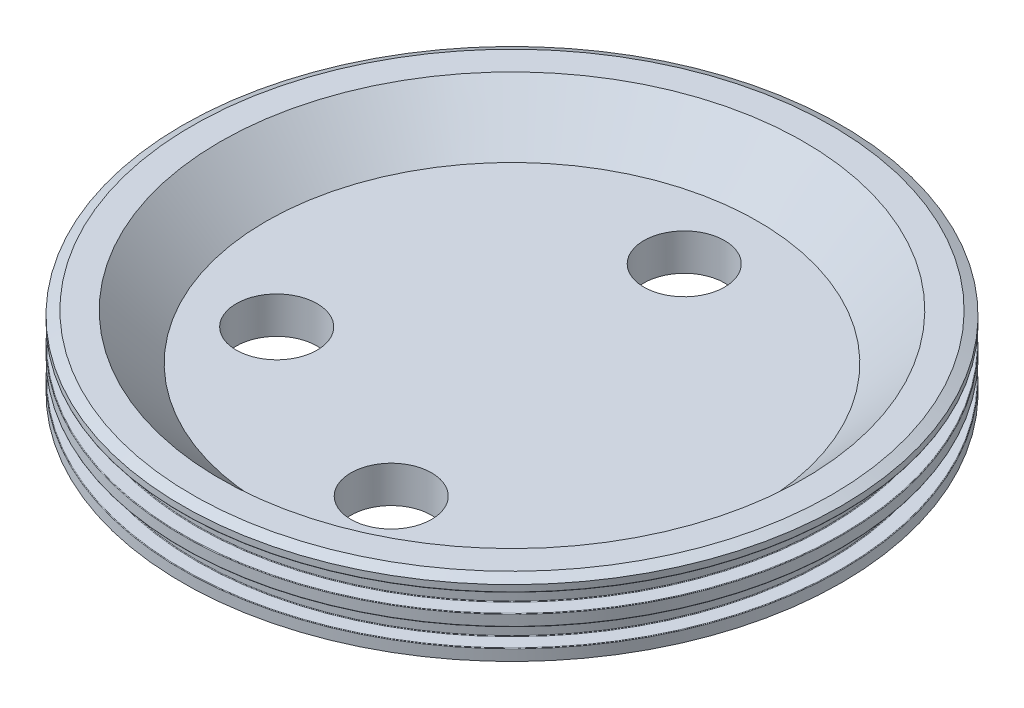
SolidWorks part; units mm, degrees
material "6061-T6 (SS)"
ref_plane "Front Plane" through (0, 0, 0) normal (0, 0, 1) x (1, 0, 0)
ref_plane "Top Plane" through (0, 0, 0) normal (0, 1, 0) x (1, 0, 0)
ref_plane "Right Plane" through (0, 0, 0) normal (1, 0, 0) x (0, 0, -1)
sketch "Sketch1" plane through (0, 0, 0) normal (0, 0, 1) x (1, 0, 0)
  line L0 (0, 48.1922) -> (0, -25.6743) construction
  line L1 (0, 0) -> (72.898, 0)
  line L2 (72.898, 0) -> (72.898, 2.54)
  line L3 (72.898, 2.54) -> (69.6468, 2.54)
  line L4 (69.6468, 2.54) -> (69.6468, 6.604)
  line L5 (69.6468, 6.604) -> (72.898, 6.604)
  line L6 (72.898, 6.604) -> (72.898, 9.144)
  line L7 (72.898, 9.144) -> (69.6468, 9.144)
  line L8 (64.5668, 15.748) -> (64.5668, 5.588)
  line L9 (64.5668, 5.588) -> (0, 5.588)
  line L10 (0, 5.588) -> (0, 0)
  line L11 (69.6468, 9.144) -> (69.6468, 13.208)
  line L12 (69.6468, 13.208) -> (72.898, 13.208)
  line L13 (72.898, 13.208) -> (72.898, 15.748)
  line L14 (72.898, 15.748) -> (64.5668, 15.748)
  dimension "D1" = 145.796
  dimension "D2" = 4.064
  dimension "D5" = 5.588
  dimension "D7" = 4.064
  dimension "D3" = 2.54
  dimension "D4" = 2.54
  dimension "D6" = 69.6468
  dimension "D8" = 5.08
revolve "Revolve1" add sketch "Sketch1" angle 360 about L0
sketch "Sketch6" plane through (0, 0, 0) normal (0, -1, 0) x (1, 0, 0)
  circle A0 centre (0, 0) radius 66.04
  dimension "D1" = 132.08
extrude "Boss-Extrude1" add sketch "Sketch6" along normal blind 2.54
fillet "CNC ID Fillet" radius 0.127 5 edges at (-69.6468, 6.604, 0) (-69.6468, 2.54, 0) (66.04, 0, 0) (-69.6468, 13.208, 0) (-69.6468, 9.144, 0)
fillet "CNC OD Fillet" radius 0.127 5 edges at (-72.898, 6.604, 0) (-72.898, 2.54, 0) (-72.898, 9.144, 0) (-72.898, 13.208, 0) (66.04, -2.54, 0)
chamfer "CNC Chamfers" distance 1.016 angle 65 1 edges at (-72.898, 15.748, 0) first distance on face at (-72.898, 13.335, 0)
hole_wizard "Pipe Tap Drill for 1/2 Tap - Fill Valve" positions "Sketch13" profile "Sketch14" hole size "1/2" standard "ANSI Inch" end condition through all
sketch "Sketch13" plane through (0, -2.54, 0) normal (0, -1, 0) x (-1, 0, 0)
  point P4 (0, 38.1)
  dimension "D1" = 38.1
sketch "Sketch14" plane through (0, -2.54, -38.1) normal (1, 0, 0) x (0, 0, -1)
  line L0 (0, 0) -> (0, 18.288)
  line L1 (0, 18.288) -> (8.9281, 18.288)
  line L2 (8.9281, 18.288) -> (8.9281, 0)
  line L5 (8.9281, 0) -> (0, 0)
  line L11 (0, -6.35) -> (0, 107.95) construction
  dimension "Thru Hole Dia." = 17.8562
  dimension "Thru Hole Depth" = 18.288
hole_wizard "Pipe Tap Drill for 1/4 Tap - Solenoid Valve" positions "Sketch15" profile "Sketch16" hole size "1/2" standard "ANSI Inch" end condition through all
sketch "Sketch15" plane through (0, -2.54, 0) normal (0, -1, 0) x (-1, 0, 0)
  line L2 (-12.0892, -38.8003) -> (0, 0) construction
  line L3 (0, 0) -> (0, -38.8003) construction
  point P4 (-12.0892, -38.8003)
  dimension "D1" = 17.306
  dimension "D2" = 40.64
  dimension "D3" = 38.8003
sketch "Sketch16" plane through (12.0892, -2.54, 38.8003) normal (1, 0, 0) x (0, 0, -1)
  line L0 (0, 0) -> (0, 18.288)
  line L1 (0, 18.288) -> (8.9281, 18.288)
  line L2 (8.9281, 18.288) -> (8.9281, 0)
  line L5 (8.9281, 0) -> (0, 0)
  line L11 (0, -6.35) -> (0, 107.95) construction
  dimension "Thru Hole Dia." = 17.8562
  dimension "Thru Hole Depth" = 18.288
hole_wizard "Pipe Tap Drill for 1/2 Tap - Cryo Valve" positions "Sketch17" profile "Sketch18" hole size "1/2" standard "ANSI Inch" end condition through all
sketch "Sketch17" plane through (0, -2.54, 0) normal (0, -1, 0) x (-1, 0, 0)
  line L0 (32.9956, -19.05) -> (17.2813, -19.05) construction
  line L2 (32.9956, -19.05) -> (0, 0) construction
  point P4 (32.9956, -19.05)
  dimension "D1" = 30
  dimension "D2" = 38.1
sketch "Sketch18" plane through (-32.9956, -2.54, 19.05) normal (1, 0, 0) x (0, 0, -1)
  line L0 (0, 0) -> (0, 18.288)
  line L1 (0, 18.288) -> (8.9281, 18.288)
  line L2 (8.9281, 18.288) -> (8.9281, 0)
  line L5 (8.9281, 0) -> (0, 0)
  line L11 (0, -6.35) -> (0, 107.95) construction
  dimension "Thru Hole Dia." = 17.8562
  dimension "Thru Hole Depth" = 18.288
chamfer "Chamfer1" distance 10.16 angle 45 1 edges at (-64.5668, 5.588, 0)
equation "\"D6@Sketch1\"=5.484/2"
